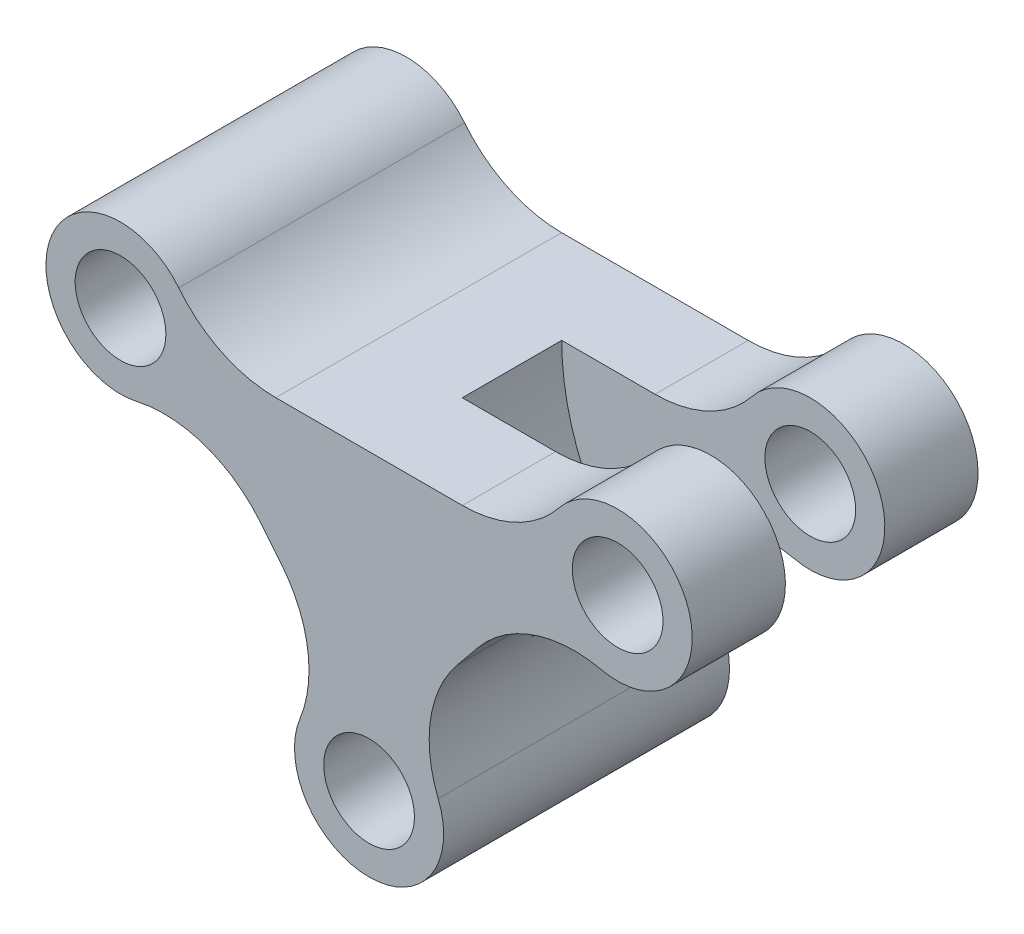
SolidWorks part; units mm, degrees
ref_plane "Plan de face" through (0, 0, 0) normal (0, 0, 1) x (1, 0, 0)
ref_plane "Plan de dessus" through (0, 0, 0) normal (0, 1, 0) x (1, 0, 0)
ref_plane "Plan de droite" through (0, 0, 0) normal (1, 0, 0) x (0, 0, -1)
sketch "Esquisse2" plane through (0, 0, 0) normal (0, 0, 1) x (1, 0, 0)
  line L0 (-8.175, 5) -> (8.175, 5)
  line L1 (8.175, 5) -> (0, -5)
  line L2 (0, -5) -> (-8.175, 5)
  line L3 (0, 0) -> (-8.175, 5) construction
  line L4 (0, 0) -> (8.175, 5) construction
  circle A0 centre (-10, 5) radius 3
  circle A1 centre (-10, 5) radius 1.825
  circle A2 centre (10, 5) radius 3
  circle A3 centre (10, 5) radius 1.825
  circle A4 centre (0, -6.825) radius 3
  circle A5 centre (0, -6.825) radius 1.825
  dimension "D2" = 3.65
  dimension "D3" = 6
  dimension "D1" = 5
  dimension "D4" = 5
  dimension "D5" = 10
extrude "Boss.-Extru.1" add sketch "Esquisse2" along normal blind 11.5 contours A4 L1 A2 L0 A0 L2 | L1 A5 L2 A4 | L1 A4 L2 | A3 | A1
ref_plane "Plan1" through (0, 0, 3.75) normal (0, 0, 1) x (1, 0, 0)
sketch "Esquisse3" plane through (0, 0, 3.75) normal (0, 0, 1) x (1, 0, 0)
  circle A0 centre (10, 5) radius 10
  dimension "D1" = 20
extrude "Enlèv. mat.-Extru.1" cut sketch "Esquisse3" along normal blind 4
fillet "Congé1" radius 5 6 edges at (-7, 5, 5.75) (-7.2311, 3.8454, 5.75) (-0.8581, -3.9503, 5.75) (7.2311, 3.8454, 9.625) (7, 5, 9.625) (0.8581, -3.9503, 5.75)
fillet "Fillet1" radius 5 2 edges at (7, 5, 1.875) (7.2311, 3.8454, 1.875)
